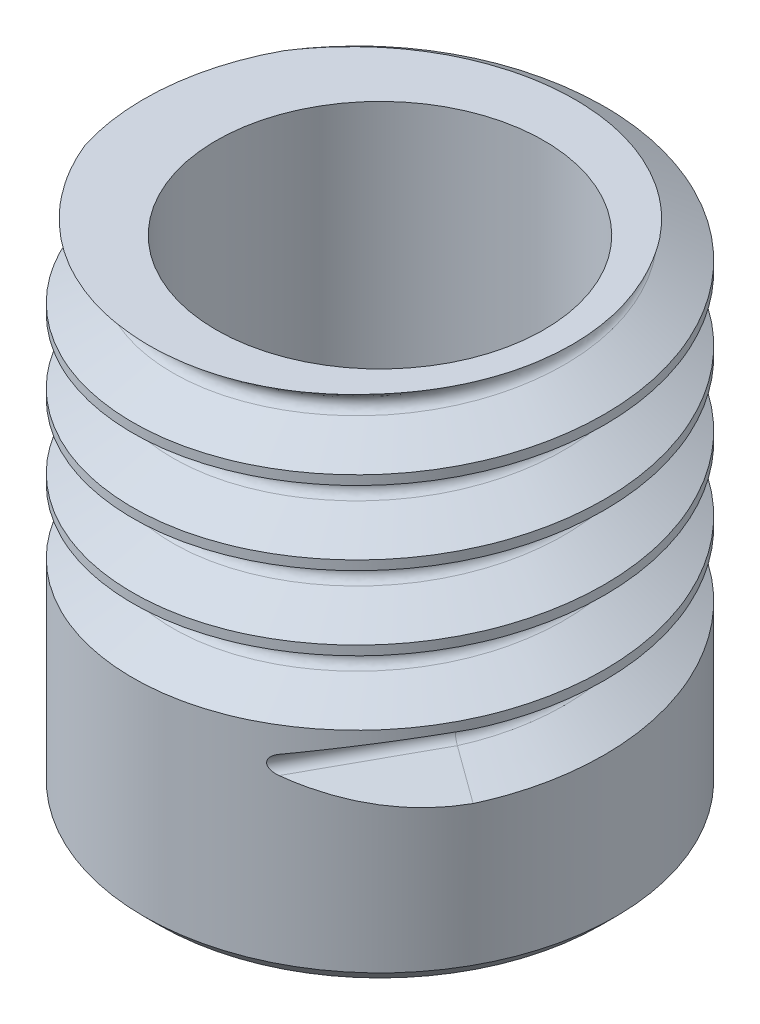
SolidWorks part; units mm, degrees
material "Plain Carbon Steel"
ref_plane "Front Plane" through (0, 0, 0) normal (0, 0, 1) x (1, 0, 0)
ref_plane "Top Plane" through (0, 0, 0) normal (0, 1, 0) x (1, 0, 0)
ref_plane "Right Plane" through (0, 0, 0) normal (1, 0, 0) x (0, 0, -1)
sketch "Sketch1" plane through (0, 0, 0) normal (0, 1, 0) x (1, 0, 0)
  circle A0 centre (0, 0) radius 4
  dimension "D1" = 8
extrude "Base" add sketch "Sketch1" along normal blind 8.255
ref_plane "Plane1" through (0, 9.525, 0) normal (0, 1, 0) x (1, 0, 0)
sketch "Sketch2" plane through (0, 9.525, 0) normal (0, 1, 0) x (1, 0, 0)
  circle A0 centre (0, 0) radius 4
curve "Helix/Spiral1" pitch 1.25 height 6.35 radius 4 centre (0, 9.525, 0) axis (0, -1, 0) start towards (1, 0, 0)
sketch "Sketch5" plane through (0, 0, 0) normal (0, -1, 0) x (1, 0, 0)
  circle A0 centre (0, 0) radius 1.27
  dimension "D1" = 2.54
extrude "RodHole" cut sketch "Sketch5" against normal blind 12.7
sketch "Sketch7" plane through (0, 8.255, 0) normal (0, 1, 0) x (1, 0, 0)
  circle A0 centre (0, 0) radius 2.7781
  dimension "D1" = 5.5562
extrude "BackBore" cut sketch "Sketch7" against normal blind 6.35
sketch "Sketch3" plane through (0, 0, 0) normal (0, 0, 1) x (1, 0, 0)
  line L0 (4.1353, 8.9005) -> (4.1353, 10.1495)
  line L1 (4.1353, 10.1495) -> (3.3237, 9.6809)
  line L2 (3.3237, 9.3691) -> (4.1353, 8.9005)
  line L3 (3.0537, 9.525) -> (4.1353, 9.525) construction
  arc A0 (3.3237, 9.6809) -> (3.3237, 9.3691) centre (3.4137, 9.525) ccw
  spline S0 degree 3 poles (-995.7614, -11.9206) (-140.409, 11.7078) (15.6467, 10.4831) (2.8947, 9.3682) (1.5554, 9.2898) (-0.0223, 9.2114) (-1.5966, 9.133) (-2.9261, 9.0546) (-3.8072, 8.9762) (-4.1046, 8.8978) (-3.7729, 8.8194) (-2.8629, 8.741) (-1.5141, 8.6627) (0.0669, 8.5843) (1.6375, 8.5059) (2.9572, 8.4275) (3.8236, 8.3491) (4.1039, 8.2707) (3.7551, 8.1923) (2.8308, 8.1139) (1.4725, 8.0355) (-0.1114, 7.9571) (-1.6783, 7.8787) (-2.988, 7.8003) (-3.8396, 7.7219) (-4.1027, 7.6435) (-3.7369, 7.5651) (-2.7983, 7.4867) (-1.4308, 7.4083) (0.156, 7.3299) (1.7189, 7.2515) (3.0183, 7.1731) (3.8551, 7.0948) (4.101, 7.0164) (3.7183, 6.938) (2.7656, 6.8596) (1.389, 6.7812) (-0.2005, 6.7028) (-1.7593, 6.6244) (-3.0484, 6.546) (-3.8702, 6.4676) (-4.0988, 6.3892) (-3.6991, 6.3108) (-2.7325, 6.2324) (-1.3469, 6.154) (0.245, 6.0756) (1.7995, 5.9972) (3.0781, 5.9188) (3.8848, 5.8404) (4.0962, 5.762) (3.6796, 5.6836) (2.699, 5.6052) (1.3048, 5.5269) (-0.2895, 5.4485) (-1.8394, 5.3701) (-3.1074, 5.2917) (-3.899, 5.2133) (-4.093, 5.1349) (-3.6596, 5.0565) (-2.6653, 4.9781) (-1.2624, 4.8997) (0.334, 4.8213) (1.8792, 4.7429) (3.1363, 4.6645) (3.9127, 4.5861) (4.0894, 4.5077) (3.6392, 4.4293) (2.6312, 4.3509) (1.2199, 4.2725) (-0.3784, 4.1941) (-1.9187, 4.1157) (-3.1649, 4.0373) (-3.926, 3.959) (-4.0853, 3.8806) (-3.6184, 3.8022) (-2.5969, 3.7238) (-1.1773, 3.6454) (0.4227, 3.567) (1.958, 3.4886) (3.1931, 3.4102) (3.9386, 3.3318) (6.307, 2.0338) (-240.7132, 0.5764) (1002.8384, 39.1754) knots -0.490327 -0.490327 -0.490327 -0.490327 0.012346 0.024691 0.037037 0.049383 0.061728 0.074074 0.08642 0.098765 0.111111 0.123457 0.135802 0.148148 0.160494 0.17284 0.185185 0.197531 0.209877 0.222222 0.234568 0.246914 0.259259 0.271605 0.283951 0.296296 0.308642 0.320988 0.333333 0.345679 0.358025 0.37037 0.382716 0.395062 0.407407 0.419753 0.432099 0.444444 0.45679 0.469136 0.481481 0.493827 0.506173 0.518519 0.530864 0.54321 0.555556 0.567901 0.580247 0.592593 0.604938 0.617284 0.62963 0.641975 0.654321 0.666667 0.679012 0.691358 0.703704 0.716049 0.728395 0.740741 0.753086 0.765432 0.777778 0.790123 0.802469 0.814815 0.82716 0.839506 0.851852 0.864198 0.876543 0.888889 0.901235 0.91358 0.925926 0.938272 0.950617 0.962963 0.975309 0.987654 1.576951 1.576951 1.576951 1.576951 only from (4, 9.525) to (3.5052, 3.175) construction
  spline S1 degree 3 poles (4, 9.525) (4, 9.499) (3.7903, 9.4465) (2.8947, 9.3682) (1.5554, 9.2898) (-0.0223, 9.2114) (-1.5966, 9.133) (-2.9261, 9.0546) (-3.8072, 8.9762) (-4.1046, 8.8978) (-3.7729, 8.8194) (-2.8629, 8.741) (-1.5141, 8.6627) (0.0669, 8.5843) (1.6375, 8.5059) (2.9572, 8.4275) (3.8236, 8.3491) (4.1039, 8.2707) (3.7551, 8.1923) (2.8308, 8.1139) (1.4725, 8.0355) (-0.1114, 7.9571) (-1.6783, 7.8787) (-2.988, 7.8003) (-3.8396, 7.7219) (-4.1027, 7.6435) (-3.7369, 7.5651) (-2.7983, 7.4867) (-1.4308, 7.4083) (0.156, 7.3299) (1.7189, 7.2515) (3.0183, 7.1731) (3.8551, 7.0948) (4.101, 7.0164) (3.7183, 6.938) (2.7656, 6.8596) (1.389, 6.7812) (-0.2005, 6.7028) (-1.7593, 6.6244) (-3.0484, 6.546) (-3.8702, 6.4676) (-4.0988, 6.3892) (-3.6991, 6.3108) (-2.7325, 6.2324) (-1.3469, 6.154) (0.245, 6.0756) (1.7995, 5.9972) (3.0781, 5.9188) (3.8848, 5.8404) (4.0962, 5.762) (3.6796, 5.6836) (2.699, 5.6052) (1.3048, 5.5269) (-0.2895, 5.4485) (-1.8394, 5.3701) (-3.1074, 5.2917) (-3.899, 5.2133) (-4.093, 5.1349) (-3.6596, 5.0565) (-2.6653, 4.9781) (-1.2624, 4.8997) (0.334, 4.8213) (1.8792, 4.7429) (3.1363, 4.6645) (3.9127, 4.5861) (4.0894, 4.5077) (3.6392, 4.4293) (2.6312, 4.3509) (1.2199, 4.2725) (-0.3784, 4.1941) (-1.9187, 4.1157) (-3.1649, 4.0373) (-3.926, 3.959) (-4.0853, 3.8806) (-3.6184, 3.8022) (-2.5969, 3.7238) (-1.1773, 3.6454) (0.4227, 3.567) (1.958, 3.4886) (3.1931, 3.4102) (3.9386, 3.3318) (4.0814, 3.2535) (3.7567, 3.201) (3.5052, 3.175) knots 0 0 0 0 0.012346 0.024691 0.037037 0.049383 0.061728 0.074074 0.08642 0.098765 0.111111 0.123457 0.135802 0.148148 0.160494 0.17284 0.185185 0.197531 0.209877 0.222222 0.234568 0.246914 0.259259 0.271605 0.283951 0.296296 0.308642 0.320988 0.333333 0.345679 0.358025 0.37037 0.382716 0.395062 0.407407 0.419753 0.432099 0.444444 0.45679 0.469136 0.481481 0.493827 0.506173 0.518519 0.530864 0.54321 0.555556 0.567901 0.580247 0.592593 0.604938 0.617284 0.62963 0.641975 0.654321 0.666667 0.679012 0.691358 0.703704 0.716049 0.728395 0.740741 0.753086 0.765432 0.777778 0.790123 0.802469 0.814815 0.82716 0.839506 0.851852 0.864198 0.876543 0.888889 0.901235 0.91358 0.925926 0.938272 0.950617 0.962963 0.975309 0.987654 1 1 1 1 construction
  point P2 (4, 9.525)
  dimension "D4" = 0.18
  dimension "D1" = 60
  dimension "D2" = 1.249
  dimension "D3" = 0.1353
sweep "MainThread" cut profiles "Sketch3" path "Helix/Spiral1"
sketch "Sketch8" plane through (0, 0, 0) normal (0.4818, 0, -0.8763) x (-0.8763, 0, -0.4818)
  line L3 (-4, 2.6282) -> (-3.3238, 3.0188)
  line L4 (-3.3236, 3.3306) -> (-4, 3.7212)
  line L5 (-4, 3.7212) -> (-4, 2.6282)
  line L6 (-4, 2.6282) -> (-3.3238, 3.0188)
  line L7 (-3.3236, 3.3306) -> (-4, 3.7212)
  line L8 (-4, 3.7212) -> (-4, 2.6282)
  arc A0 (-3.3238, 3.0188) -> (-3.3236, 3.3306) centre (-3.4136, 3.1747) ccw
  arc A1 (-3.3238, 3.0188) -> (-3.3236, 3.3306) centre (-3.4136, 3.1747) ccw
  dimension "D1" = 0
extrude "ThreadLeadOut" cut sketch "Sketch8" against normal through all
chamfer "Chamfer1" distance 0.254 angle 45 2 edges at (0, 0, 4) (0, 0, -1.27)
